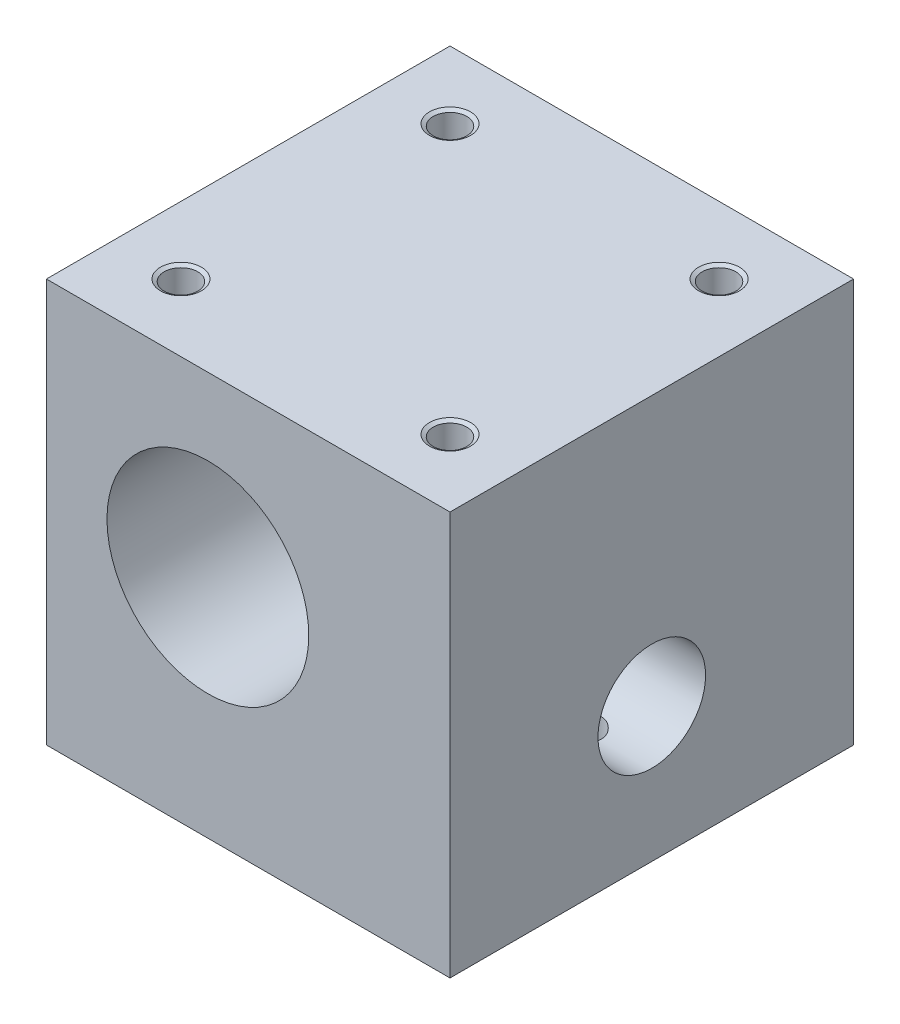
SolidWorks part; units mm, degrees
material "Lega 1060"
ref_plane "Piano frontale" through (0, 0, 0) normal (0, 0, 1) x (1, 0, 0)
ref_plane "Piano superiore" through (0, 0, 0) normal (0, 1, 0) x (1, 0, 0)
ref_plane "Piano destro" through (0, 0, 0) normal (1, 0, 0) x (0, 0, -1)
sketch "Schizzo1" plane through (0, 0, 0) normal (0, 0, 1) x (1, 0, 0)
  line L0 (12, 6.5764) -> (12, 28.444) construction
  line L1 (0, 0) -> (30, 0)
  line L2 (0, 0) -> (0, 30)
  line L3 (0, 30) -> (30, 30)
  line L4 (30, 0) -> (30, 30)
  line L5 (6.315, 16.8) -> (24.6155, 16.8) construction
  circle A0 centre (12, 16.8) radius 7.5
  dimension "D3" = 15
  dimension "D1" = 30
  dimension "D2" = 30
  dimension "D4" = 12
  dimension "D5" = 13.2
extrude "Estrusione-Estrusione1" add sketch "Schizzo1" along normal blind 30
sketch "Schizzo3" plane through (30, 0, 0) normal (1, 0, 0) x (0, 0, -1)
  line L2 (-15, 10.16) -> (-15, 24.3684) construction
  line L3 (-30, 0) -> (-30, 30) construction
  line L4 (0, 0) -> (0, 30) construction
  line L5 (-30, 0) -> (0, 0) construction
  point P0 (-15, 10)
  dimension "D1" = 10
hole_wizard "Foro Ø8.0 (8)-1" positions "Schizzo5" profile "Schizzo4" hole size "Ø8.0" standard "ISO"
sketch "Schizzo5" plane through (30, 0, 0) normal (1, 0, 0) x (0, 0, -1)
  point P0 (-15, 10)
sketch "Schizzo4" plane through (30, 10, 15) normal (0, 1, 0) x (0, 0, -1)
  line L0 (0, 0) -> (0, 12.4034)
  line L1 (0, 12.4034) -> (4, 10)
  line L2 (4, 10) -> (4, 0)
  line L5 (4, 0) -> (0, 0)
  line L10 (0, 12.4034) -> (-4, 10) construction
  line L11 (0, -6.35) -> (0, 107.95) construction
  dimension "Hole Dia." = 8
  dimension "Hole Depth" = 10
  dimension "Drill Angle" = 118
sketch "Schizzo6" plane through (0, 30, 0) normal (0, 1, 0) x (1, 0, 0)
  line L0 (-7.6843, -25) -> (41.504, -25) construction
  line L1 (0, -30) -> (0, 0) construction
  line L2 (30, -30) -> (0, -30) construction
  point P0 (5, -25)
  point P1 (25, -25)
  dimension "D1" = 20
  dimension "D2" = 5
  dimension "D3" = 5
hole_wizard "Foro filettato M3-1" positions "Schizzo8" profile "Schizzo7" tap size "M3" standard "ISO"
sketch "Schizzo8" plane through (0, 30, 0) normal (0, 1, 0) x (1, 0, 0)
  point P0 (5, -25)
  point P3 (25, -25)
sketch "Schizzo7" plane through (5, 30, 25) normal (1, 0, 0) x (0, 0, 1)
  line L0 (0, 0) -> (0, 9.2511)
  line L1 (0, 9.2511) -> (1.25, 8.5)
  line L2 (1.25, 8.5) -> (1.25, 0.1588)
  line L3 (1.25, 0.1588) -> (1.525, 0)
  line L5 (1.525, 0) -> (0, 0)
  line L6 (-1.25, 0.1588) -> (-1.525, 0) construction
  line L10 (0, 9.2511) -> (-1.25, 8.5) construction
  line L11 (0, -6.35) -> (0, 107.95) construction
  dimension "Tap Drill Dia." = 2.5
  dimension "Tap Drill Depth" = 8.5
  dimension "Near C'Sink Dia." = 3.05
  dimension "Near C'Sink Angle" = 120
  dimension "Drill Angle" = 118
cosmetic thread "Filettatura del foro1" parameters "D1"=6, "D2"=3
cosmetic thread "Filettatura del foro2" parameters "D1"=6, "D2"=3
ref_plane "Piano1" through (0, 0, 15) normal (0, 0, 1) x (1, 0, 0)
mirror "Specchia1" about plane through (0, 0, 15) normal (0, 0, 1) of "Foro filettato M3-1"
hole_wizard "Foro filettato M3-2" positions "Schizzo10" profile "Schizzo11" tap size "M3" standard "ISO"
sketch "Schizzo10" plane through (0, 0, 0) normal (0, -1, 0) x (-1, 0, 0)
  line L0 (0, 0) -> (-30, 0) construction
  line L1 (-30, -30) -> (-30, 0) construction
  point P0 (-25, -15)
  dimension "D1" = 15
  dimension "D2" = 5
sketch "Schizzo11" plane through (25, 0, 15) normal (1, 0, 0) x (0, 0, -1)
  line L0 (0, 0) -> (0, 9.2511)
  line L1 (0, 9.2511) -> (1.25, 8.5)
  line L2 (1.25, 8.5) -> (1.25, 0.1588)
  line L3 (1.25, 0.1588) -> (1.525, 0)
  line L5 (1.525, 0) -> (0, 0)
  line L6 (-1.25, 0.1588) -> (-1.525, 0) construction
  line L10 (0, 9.2511) -> (-1.25, 8.5) construction
  line L11 (0, -6.35) -> (0, 107.95) construction
  dimension "Tap Drill Dia." = 2.5
  dimension "Tap Drill Depth" = 8.5
  dimension "Near C'Sink Dia." = 3.05
  dimension "Near C'Sink Angle" = 120
  dimension "Drill Angle" = 118
sketch "Schizzo12" plane through (0, 0, 30) normal (0, 0, 1) x (1, 0, 0)
  line L0 (30, 0) -> (0, 30) construction
  line L1 (0, 0) -> (30, 30) construction
  point P8 (15, 15)
